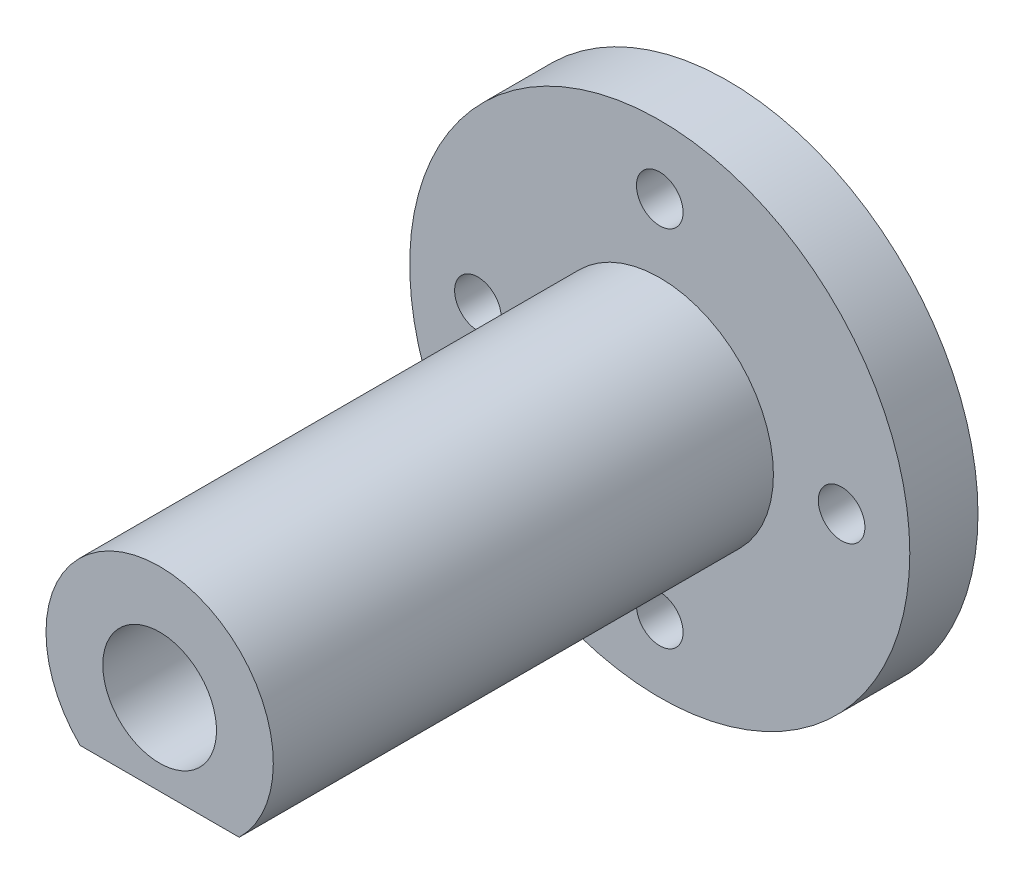
SolidWorks part; units mm, degrees
ref_plane "Front Plane" through (0, 0, 0) normal (1, 0, 0) x (0, 1, 0)
ref_plane "Top Plane" through (0, 0, 0) normal (0, 0, 1) x (0, 1, 0)
ref_plane "Right Plane" through (0, 0, 0) normal (0, 1, 0) x (-1, 0, 0)
sketch "Sketch1" plane through (0, 0, 0) normal (0, 0, 1) x (0, 1, 0)
  line L0 (0, 8) -> (0, 0) construction
  circle A0 centre (0, 0) radius 11
  circle A1 centre (0, 8) radius 1.025
  circle A2 centre (0, 0) radius 4.25
  circle A3 centre (8, 0) radius 1.025
  circle A4 centre (0, -8) radius 1.025
  circle A5 centre (-8, 0) radius 1.025
  point P15 (0, 0)
  dimension "D1" = 22
  dimension "D2" = 8
  dimension "D3" = 2.05
  dimension "D4" = 8.5
  dimension "D5" = 4
extrude "Boss-Extrude1" add sketch "Sketch1" along normal blind 3
sketch "Sketch2" plane through (0, 0, 3) normal (0, 0, 1) x (1, 0, 0)
  circle A1 centre (0, 0) radius 5
  circle A2 centre (0, 0) radius 2.5
  dimension "D1" = 5
  dimension "D2" = 10
extrude "Boss-Extrude2" add sketch "Sketch2" along normal offset from surface (22 mm away) 25 up to face at (11, 0, 0)
sketch "Sketch3" plane through (0, 0, 25) normal (0, 0, 1) x (1, 0, 0)
  line L0 (3.5, -3.5707) -> (-3.5, -3.5707)
  circle A0 centre (0, 0) radius 5 construction
  circle A1 centre (0, 0) radius 5 construction
  arc A2 (-3.5, -3.5707) -> (3.5, -3.5707) centre (0, 0) ccw
  dimension "D1" = 7
extrude "Cut-Extrude1" cut sketch "Sketch3" against normal blind 10
